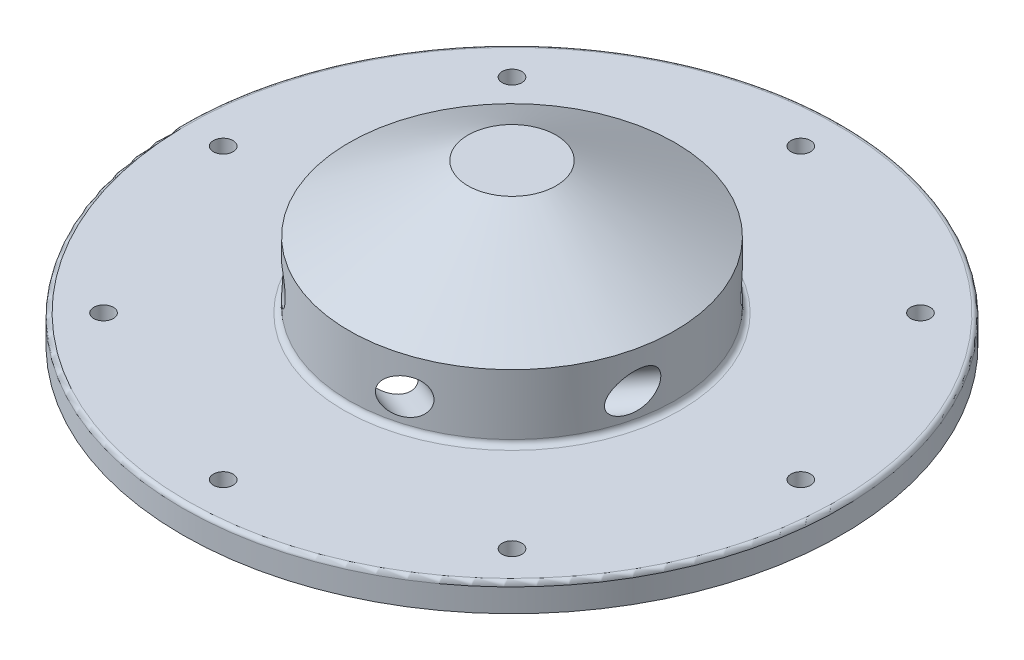
SolidWorks part; units mm, degrees
material "7075-T6 (SN)"
ref_plane "Front Plane" through (0, 0, 0) normal (0, 0, 1) x (1, 0, 0)
ref_plane "Top Plane" through (0, 0, 0) normal (0, 1, 0) x (1, 0, 0)
ref_plane "Right Plane" through (0, 0, 0) normal (1, 0, 0) x (0, 0, -1)
sketch "Sketch2" plane through (0, 0, 0) normal (0, 1, 0) x (1, 0, 0)
  circle A0 centre (0, 0) radius 38.0403
  dimension "D1" = 76.0806
extrude "Boss-Extrude1" add sketch "Sketch2" along normal blind 3.175
hole_wizard "Tap Drill for #4-40 Tap1" positions "Sketch3" profile "Sketch4" hole size "#4-40" standard "ANSI Inch" end condition through all
sketch "Sketch3" plane through (0, 0, 0) normal (0, -1, 0) x (-1, 0, 0)
  point P0 (0, -33.3375)
  dimension "D1" = 33.3375
sketch "Sketch4" plane through (0, 0, 33.3375) normal (1, 0, 0) x (0, 0, -1)
  line L0 (0, 0) -> (0, 3.175)
  line L1 (0, 3.175) -> (1.1303, 3.175)
  line L2 (1.1303, 3.175) -> (1.1303, 0)
  line L5 (1.1303, 0) -> (0, 0)
  line L11 (0, -6.35) -> (0, 107.95) construction
  dimension "Thru Hole Dia." = 2.2606
  dimension "Thru Hole Depth" = 3.175
pattern_circular "CirPattern1" count 8 over 360 about axis through (0, 0, 0) along (0, 1, 0) of "Tap Drill for #4-40 Tap1"
sketch "Sketch5" plane through (0, 3.175, 0) normal (0, 1, 0) x (1, 0, 0)
  circle A0 centre (0, 0) radius 28.575
  dimension "D1" = 57.15
sketch "Sketch7" plane through (0, 3.175, 0) normal (0, 1, 0) x (1, 0, 0)
  circle A0 centre (0, 0) radius 18.81
  dimension "D1" = 37.62
extrude "Boss-Extrude2" add sketch "Sketch7" along normal blind 7.62
sketch "Sketch8" plane through (0, 0, 0) normal (0, -1, 0) x (1, 0, 0)
  circle A0 centre (0, 0) radius 15
  dimension "D1" = 30
extrude "Cut-Extrude1" cut sketch "Sketch8" against normal blind 8.89
sketch "Sketch13" plane through (0, 10.795, 0) normal (0, 1, 0) x (1, 0, 0)
  circle A0 centre (0, 0) radius 18.81
  circle A1 centre (0, 0) radius 18.81 construction
  dimension "D1" = 0
ref_plane "Plane2" through (0, 18.415, 0) normal (0, 1, 0) x (1, 0, 0)
sketch "Sketch14" plane through (0, 18.415, 0) normal (0, 1, 0) x (1, 0, 0)
  circle A0 centre (0, 0) radius 5.08
  dimension "D1" = 10.16
loft "Loft2" add profiles "Sketch14", "Sketch13" connector at (-0.0647, 18.415, 5.0796) connector at (0, 10.795, 18.81)
fillet "Fillet1" radius 0.635 1 edges at (0, 8.89, -15)
fillet "Fillet3" radius 0.5 1 edges at (0, 3.175, 38.0403)
ref_plane "Plane4" through (0, 7.62, 0) normal (0, 1, 0) x (1, 0, 0)
fillet "Fillet2" radius 0.635 1 edges at (0, 3.175, 18.81)
ref_axis "Axis1" through (41.91, 7.62, 0) along (-1, 0, 0)
ref_plane "Plane3" through (0, 0.5104, 1.905) normal (0, 0.2588, 0.9659) x (-1, 0, 0)
sketch "Sketch16" plane through (0, 0.5104, 1.905) normal (0, 0.2588, 0.9659) x (-1, 0, 0)
  circle A0 centre (12.71, -2.7899) radius 1.98
  dimension "D1" = 3.96
  dimension "D2" = 12.71
  dimension "D3" = 2.7899
extrude "Cut-Extrude2" cut sketch "Sketch16" along normal through all
pattern_circular "CirPattern2" count 6 over 360 about axis through (0, 10.795, 0) along (0, 1, 0) of "Cut-Extrude2"
